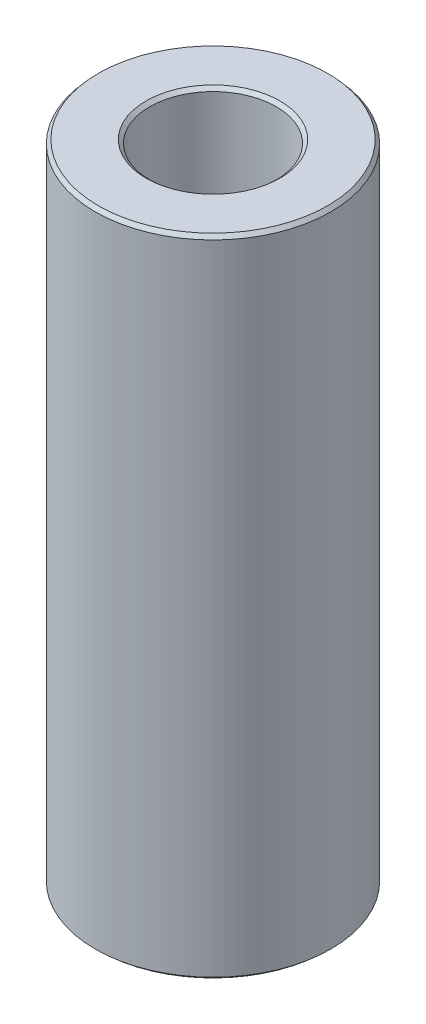
SolidWorks part; units mm, degrees
ref_plane "Front Plane" through (0, 0, 0) normal (0, 0, 1) x (1, 0, 0)
ref_plane "Top Plane" through (0, 0, 0) normal (0, 1, 0) x (1, 0, 0)
ref_plane "Right Plane" through (0, 0, 0) normal (1, 0, 0) x (0, 0, -1)
sketch "Sketch1" plane through (0, 0, 0) normal (0, 1, 0) x (1, 0, 0)
  circle A0 centre (0, 0) radius 10
  dimension "SLEEVE_OD" = 20
extrude "Boss-Extrude1" add sketch "Sketch1" along normal blind 54.7454
sketch "Sketch2" plane through (0, 0, 0) normal (0, 1, 0) x (1, 0, 0)
  circle A0 centre (0, 0) radius 5.3733
  dimension "BORE_D" = 10.7465
extrude "Cut-Extrude1" cut sketch "Sketch2" along normal through all
chamfer "Chamfer1" distance 0.3087 angle 41.505 4 edges at (0, 54.7454, 5.3733) (0, 0, 5.3733) (0, 0, 10) (0, 54.7454, 10) first distance on face at (0, 54.7454, 5.3733) first distance on face at (0, 0, 5.3733) first distance on face at (0, 54.7454, 10)
